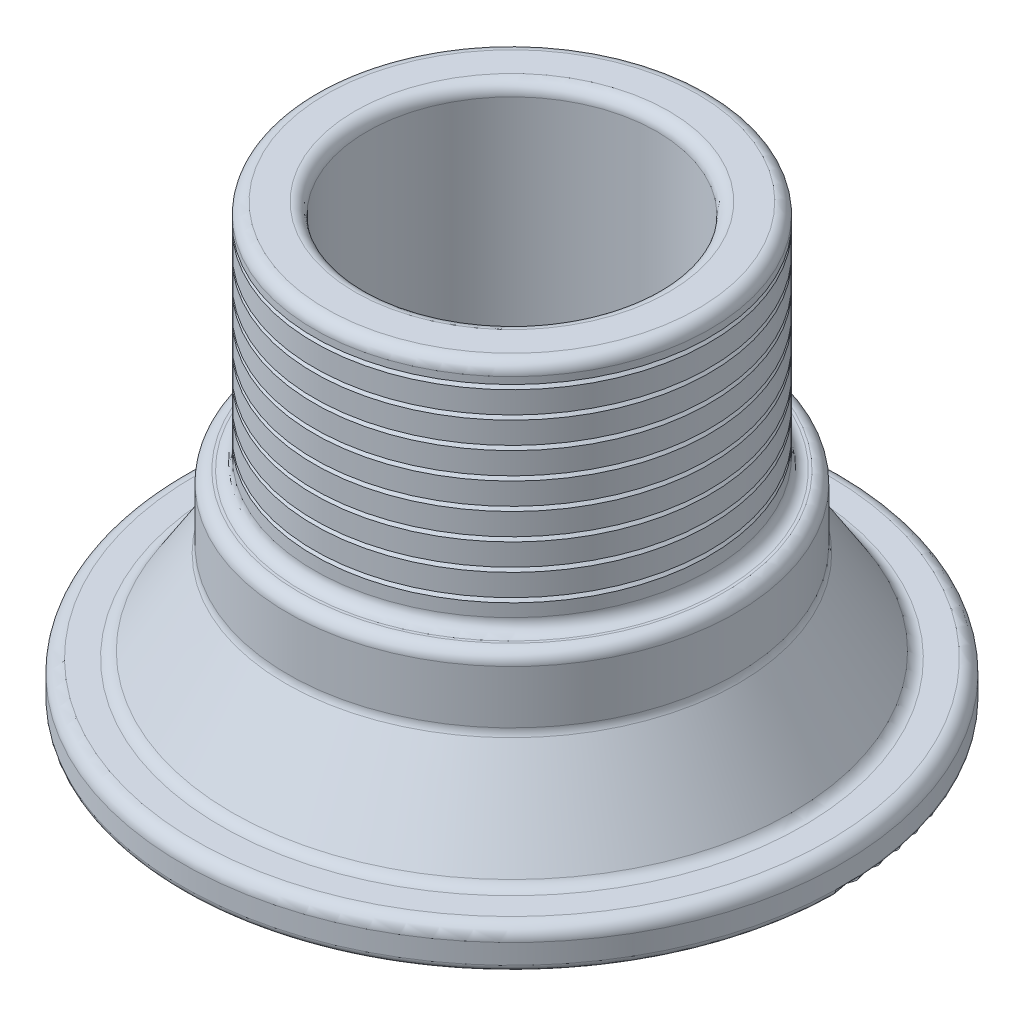
SolidWorks part; units mm, degrees
ref_plane "Front Plane" through (0, 0, 0) normal (0, 0, 1) x (1, 0, 0)
ref_plane "Top Plane" through (0, 0, 0) normal (0, 1, 0) x (1, 0, 0)
ref_plane "Right Plane" through (0, 0, 0) normal (1, 0, 0) x (0, 0, -1)
sketch "Sketch1" plane through (0, 0, 0) normal (0, 1, 0) x (1, 0, 0)
  circle A0 centre (0, 0) radius 25
  circle A1 centre (0, 0) radius 13
  dimension "D1" = 50
  dimension "D2" = 26
sketch "Sketch2" plane through (0, 0, 0) normal (0, 0, 1) x (1, 0, 0)
  line L0 (-14, 1) -> (-14, 3)
  line L1 (13, 0) -> (-13, 0) construction
  line L2 (25, 0) -> (-25, 0) construction
  line L3 (-14, 3) -> (-14, 13)
  line L8 (0, 0) -> (0, 42.8477) construction
  line L9 (-24.5, 0) -> (-15, 0)
  line L10 (-25, 0.5) -> (-25, 2)
  line L11 (-24, 3) -> (-22.0675, 3)
  line L12 (-21.2219, 3.4661) -> (-17.1545, 9.907)
  line L13 (-15, 0) -> (-14, 1)
  line L45 (-14, 13) -> (-11, 13)
  line L50 (-11, 13) -> (-11, 32.1)
  line L53 (-14.1, 33) -> (-11.9, 33)
  line L54 (-17, 10.441) -> (-17, 14.4696)
  line L55 (-16.1, 15.3696) -> (-15.9, 15.3696)
  line L56 (-15, 16.2696) -> (-15, 17.2425)
  line L57 (-15, 17.2425) -> (-14.73, 17.5826)
  line L58 (-14.73, 17.5826) -> (-15, 17.5826)
  line L59 (-15, 19.2425) -> (-14.73, 19.5826)
  line L60 (-14.73, 19.5826) -> (-15, 19.5826)
  line L61 (-15, 21.2425) -> (-14.73, 21.5826)
  line L62 (-14.73, 21.5826) -> (-15, 21.5826)
  line L63 (-15, 23.2425) -> (-14.73, 23.5826)
  line L64 (-14.73, 23.5826) -> (-15, 23.5826)
  line L65 (-15, 25.2425) -> (-14.73, 25.5826)
  line L66 (-14.73, 25.5826) -> (-15, 25.5826)
  line L67 (-15, 27.2425) -> (-14.73, 27.5826)
  line L68 (-14.73, 27.5826) -> (-15, 27.5826)
  line L69 (-15, 29.2425) -> (-14.73, 29.5826)
  line L70 (-14.73, 29.5826) -> (-15, 29.5826)
  line L71 (-15, 31.2425) -> (-14.73, 31.5826)
  line L72 (-14.73, 31.5826) -> (-15, 31.5826)
  line L73 (-15, 17.5826) -> (-15, 19.2425)
  line L74 (-15, 19.5826) -> (-15, 21.2425)
  line L75 (-15, 21.5826) -> (-15, 23.2425)
  line L76 (-15, 23.5826) -> (-15, 25.2425)
  line L77 (-15, 25.5826) -> (-15, 27.2425)
  line L78 (-15, 27.5826) -> (-15, 29.2425)
  line L79 (-15, 29.5826) -> (-15, 31.2425)
  line L80 (-15, 31.5826) -> (-15, 32.1)
  arc A0 (-25, 0.5) -> (-24.5, 0) centre (-24.5, 0.5) ccw
  arc A1 (-25, 2) -> (-24, 3) centre (-24, 2) cw
  arc A2 (-17, 10.441) -> (-17.1545, 9.907) centre (-18, 10.441) cw
  arc A3 (-22.0675, 3) -> (-21.2219, 3.4661) centre (-22.0675, 4) ccw
  arc A4 (-15.9, 15.3696) -> (-15, 16.2696) centre (-15.9, 16.2696) ccw
  arc A5 (-17, 14.4696) -> (-16.1, 15.3696) centre (-16.1, 14.4696) cw
  arc A6 (-15, 32.1) -> (-14.1, 33) centre (-14.1, 32.1) cw
  arc A7 (-11, 32.1) -> (-11.9, 33) centre (-11.9, 32.1) ccw
  point P0 (-14, 0)
  point P17 (-25, 0)
  point P20 (-25, 3)
  point P38 (-11, 33)
  dimension "D5" = 0.5
  dimension "D6" = 1
  dimension "D7" = 1
  dimension "D8" = 4
  dimension "D12" = 0.9
  dimension "D14" = 0.9
  dimension "D1" = 14
  dimension "D2" = 25
  dimension "D3" = 3
  dimension "D4" = 20
  dimension "D9" = 33
  dimension "D10" = 3
  dimension "D13" = 3
  dimension "D15" = 8
revolve "Revolve1" add sketch "Sketch2" angle 360 about L8
thread "Thread1" pitch 1.75 method extrude profile "Thread Profile1" start angle 0, offset 0, length 18, pitch 1.75, diameter 28
ref_plane "Plane1" through (14, 1, 0) normal (0, 0, 1) x (1, 0, 0)
sketch "Thread Profile1" plane through (14, 1, 0) normal (0, 0, 1) x (1, 0, 0)
  line L0 (0, 0) -> (0, 1.75) construction
  line L11 (0, 0) -> (0, 1.5312)
  line L12 (0, 1.5312) -> (-0.9472, 0.9844)
  line L13 (-0.9472, 0.9844) -> (-0.9472, 0.5469)
  line L15 (-0.9472, 0.5469) -> (0, 0)
  line L17 (-0.9472, 0.7656) -> (0, 0.7656) construction
  point P2 (0, 0)
  dimension "Pitch" = 1.75
  dimension "Profile_Angle" = 60
  dimension "Profile_Land" = 0.4375
  dimension "Profile_Height" = 0.9472
